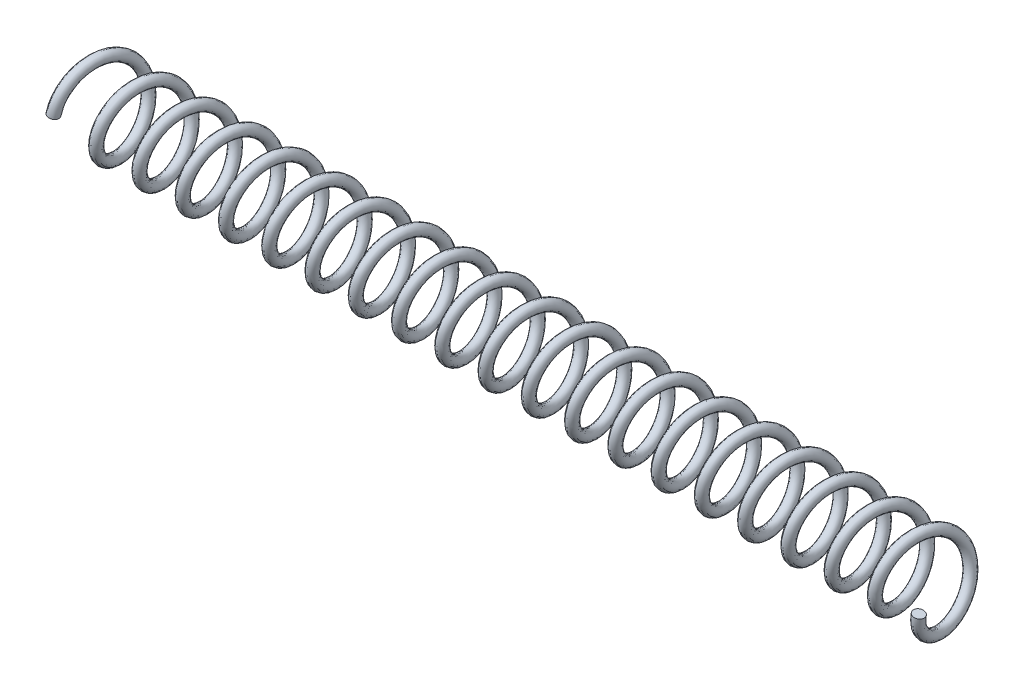
SolidWorks part; units mm, degrees
note: '?' marks a value the reader was unsure of.
ref_plane "Front Plane" through (0, 0, 0) normal (0, 0, 1) x (1, 0, 0)
ref_plane "Top Plane" through (0, 0, 0) normal (0, 1, 0) x (1, 0, 0)
ref_plane "Right Plane" through (0, 0, 0) normal (1, 0, 0) x (0, 0, -1)
sketch "Sketch1" plane through (0, 0, 0) normal (1, 0, 0) x (0, 0, -1)
  line L0 (-21.9702, 33) -> (21.4637, 33) construction
  line L1 (-21.9702, 35) -> (21.4637, 35) construction
  line L2 (-21.9702, 34) -> (21.4637, 34) construction
  circle A1 centre (-0.2533, 34.8) radius 0.125
  point P9 (0, 0)
  point P10 (-0.2533, 34)
  dimension "D4" = 0.8
  dimension "D5" = 0.25
  dimension "D1" = 33
  dimension "D2" = 2
  dimension "D3" = 1
sketch "Sketch4" plane through (0, 0, 0) normal (0, 0, 1) x (1, 0, 0)
  circle A0 centre (0, 0) radius 34
  dimension "D1" = 68
sketch "Sketch5" plane through (0, 0, 0) normal (1, 0, 0) x (0, 0, -1)
  circle A0 centre (0, 34) radius 0.8391
  point P5 (0, 0)
  point P6 (0, 0)
  point P7 (0, 0)
curve "Helix/Spiral2" pitch 1 height 20 turns 20
sweep "Sweep1" add path "Helix/Spiral2" circular profile diameter 0.25 parameters "D3"=0.25
sketch3d "3DSketch1"
  line L0 (0, 34, 0) -> (17.0473, 34, 0)
  circle A0 centre (0, 0, 0) radius 34 construction
  point P0 (0, 34, 0)
  point P4 (0, 0, 34)
ref_axis "Axis1" through (0, 34, 0) along (1, 0, 0)?
sketch3d "3DSketch2"
  spline S0 degree 2 poles (0, 0, 0) (-45.064, 0.4897, 0) (-74.5953, -29.6476, 0) knots 0 0 0 1 1 1
